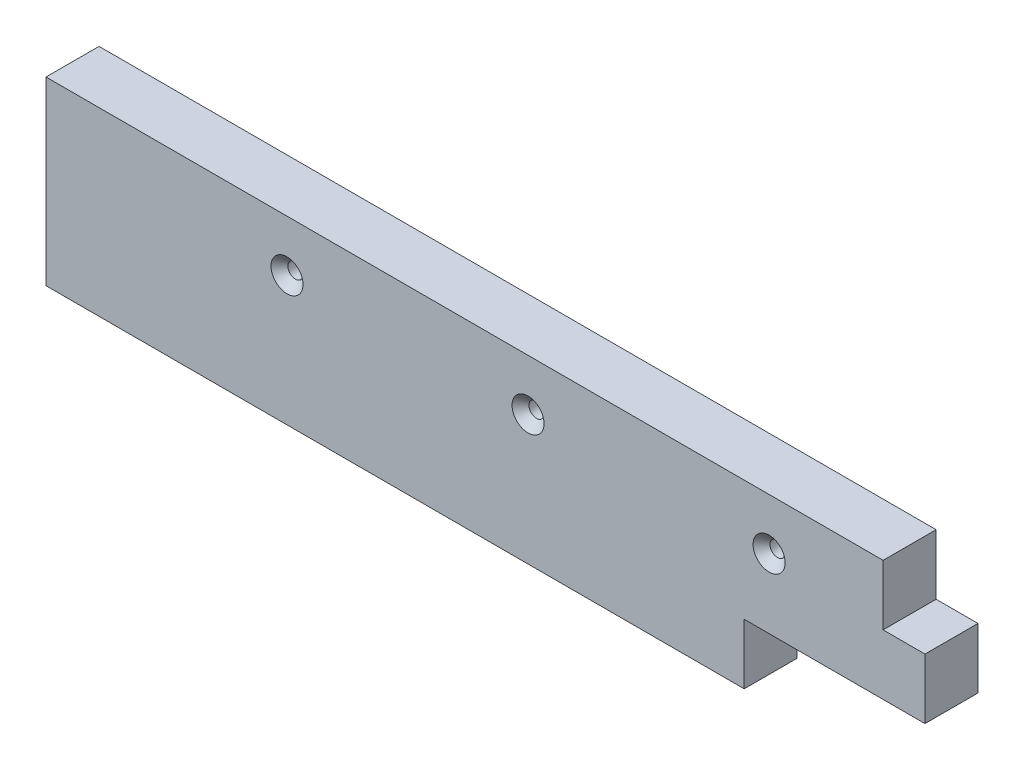
SolidWorks part; units mm, degrees
ref_plane "Front Plane" through (0, 0, 0) normal (0, 0, 1) x (1, 0, 0)
ref_plane "Top Plane" through (0, 0, 0) normal (0, 1, 0) x (1, 0, 0)
ref_plane "Right Plane" through (0, 0, 0) normal (1, 0, 0) x (0, 0, -1)
sketch "Sketch1" plane through (0, 0, 0) normal (0, 1, 0) x (1, 0, 0)
  line L1 (-185.2521, -11.176) -> (185.2521, -11.176)
  line L2 (-185.2521, -11.176) -> (-185.2521, 11.176)
  line L3 (-185.2521, 11.176) -> (185.2521, 11.176)
  line L4 (185.2521, -11.176) -> (185.2521, 11.176)
  line L5 (-185.2521, -11.176) -> (185.2521, 11.176) construction
  line L6 (-185.2521, 11.176) -> (185.2521, -11.176) construction
  point P0 (0, 0)
extrude "Boss-Extrude1" add sketch "Sketch1" along normal mid plane 76.2 contours L1 L4 L3 L2
sketch "Sketch3" plane through (0, 0, 11.176) normal (0, 0, 1) x (1, 0, 0)
  line L1 (167.6064, 12.7) -> (185.2521, 12.7)
  line L2 (185.2521, 38.1) -> (185.2521, 12.7)
  line L3 (167.6064, 12.7) -> (167.6064, 38.1)
  line L4 (167.6064, 38.1) -> (185.2521, 38.1)
  line L5 (109.0521, -12.7) -> (185.2521, -12.7)
  line L6 (109.0521, -12.7) -> (109.0521, -38.1)
  line L7 (109.0521, -38.1) -> (185.2521, -38.1)
  line L8 (185.2521, -12.7) -> (185.2521, -38.1)
  dimension "D1" = 76.2
  dimension "D2" = 25.4
hole_wizard "CSK for M6 Hex Socket Countersunk Head Screw6" positions "Sketch21" profile "Sketch20" countersink size "M6" standard "Lanco STD" end condition through all
sketch "Sketch21" plane through (0, 0, 11.176) normal (0, 0, 1) x (1, 0, 0)
  point P0 (-83.6521, 16.5075)
  point P8 (17.9479, 16.5075)
  point P11 (119.5479, 16.5075)
sketch "Sketch20" plane through (-83.6521, 16.5075, 11.176) normal (1, 0, 0) x (0, -1, 0)
  line L0 (0, 0) -> (0, 22.352)
  line L1 (0, 22.352) -> (3.2, 22.352)
  line L2 (3.2, 22.352) -> (3.2, 3.55)
  line L3 (3.2, 3.55) -> (6.75, 0)
  line L5 (6.75, 0) -> (0, 0)
  line L6 (-3.2, 3.55) -> (-6.75, 0) construction
  line L11 (0, -6.35) -> (0, 107.95) construction
  dimension "Thru Hole Dia." = 6.4
  dimension "Thru Hole Depth" = 22.352
  dimension "Near C'Sink Dia." = 13.5
  dimension "Near C'Sink Angle" = 90
extrude "Cut-Extrude1" cut sketch "Sketch3" against normal through all
